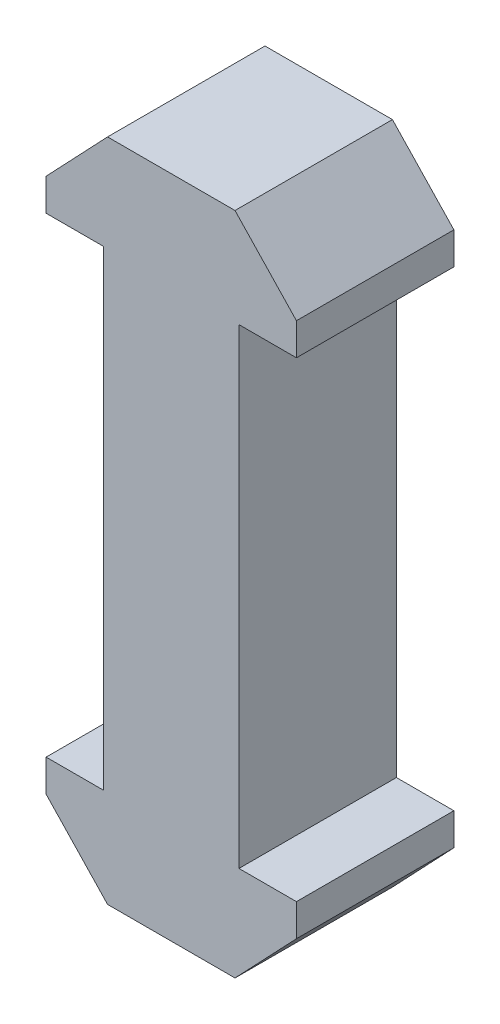
SolidWorks part; units mm, degrees
ref_plane "Front Plane" through (0, 0, 0) normal (0, 0, 1) x (1, 0, 0)
ref_plane "Top Plane" through (0, 0, 0) normal (0, 1, 0) x (1, 0, 0)
ref_plane "Right Plane" through (0, 0, 0) normal (1, 0, 0) x (0, 0, -1)
sketch "Sketch1" plane through (0, 0, 0) normal (0, 0, 1) x (1, 0, 0)
  line L3 (0, 0) -> (0, 12.835) construction
  line L8 (0, 12.835) -> (-8.6643, 12.835) construction
  line L14 (4.3, 27.7925) -> (4.3, -2.1225)
  line L15 (-4.3, 27.7925) -> (-4.3, -2.1225)
  line B0 (7.95, -2.1225) -> (7.95, -4.1625)
  line B1 (4.048, -8.2749) -> (-4.048, -8.2749)
  line B2 (-7.95, -4.1625) -> (-7.95, -2.1225)
  line B3 (-7.95, -2.1225) -> (7.95, -2.1225)
  line B4 (7.95, -4.1625) -> (4.048, -8.2749)
  line B5 (-4.048, -8.2749) -> (-7.95, -4.1625)
  line B6 (7.95, 27.7925) -> (7.95, 29.8325)
  line B7 (4.048, 33.9449) -> (-4.048, 33.9449)
  line B8 (-7.95, 29.8325) -> (-7.95, 27.7925)
  line B9 (-7.95, 27.7925) -> (7.95, 27.7925)
  line B10 (7.95, 29.8325) -> (4.048, 33.9449)
  line B11 (-4.048, 33.9449) -> (-7.95, 29.8325)
  dimension "D1" = 29.915
  dimension "D5" = 8.6
sketch_block_instance "Block1-1"
sketch_block "Block1" parameters "D1"=8.44, "D2"=2.6, "D3"=6, "D4"=16.7, "D6"=5.6686, "D7"=2.0404, "D8"=8.0963, "D9"=15.9, "D5"=2.4157
sketch_block_instance "Block1-5"
extrude "Boss-Extrude1" add sketch "Sketch1" along normal mid plane 10 contours B0 | L15 B0 L14 | B11 B8 B9 B6 B10 B7 region at (0, 12.835, 0) region at (0, 30.5341, 0) region at (0, -4.864, 0)
equation "\"SmallJarHeight\"=65"
